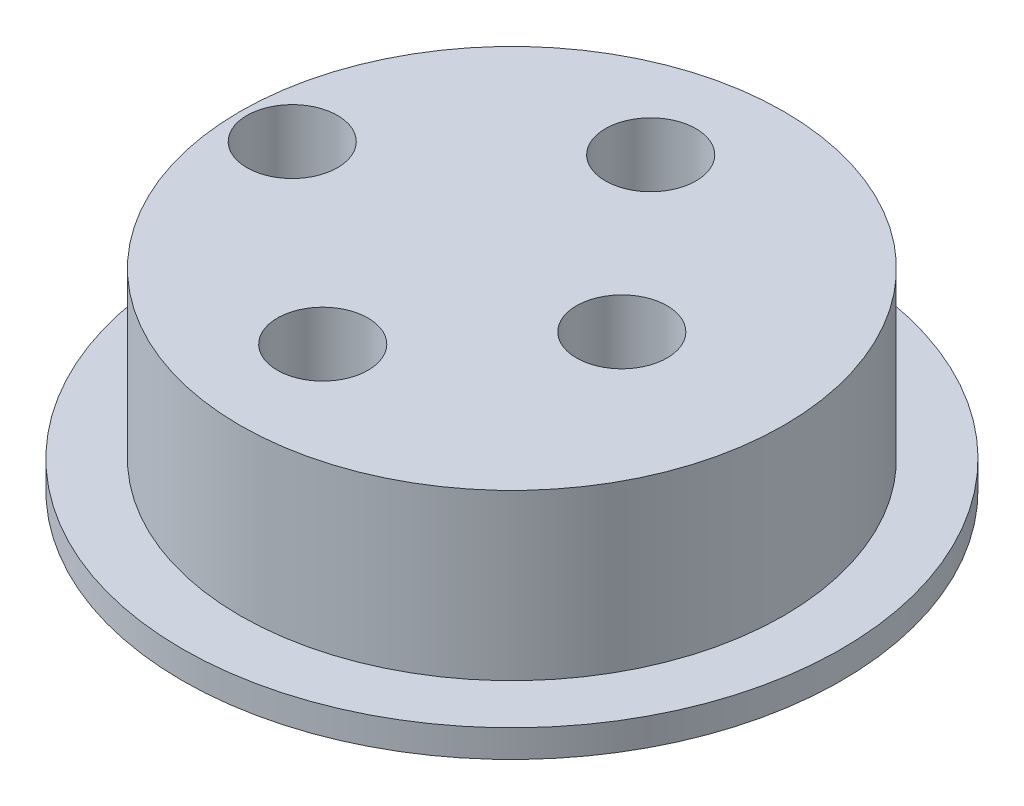
SolidWorks part; units mm, degrees
ref_plane "Front Plane" through (0, 0, 0) normal (0, 0, 1) x (1, 0, 0)
ref_plane "Top Plane" through (0, 0, 0) normal (0, 1, 0) x (1, 0, 0)
ref_plane "Right Plane" through (0, 0, 0) normal (1, 0, 0) x (0, 0, -1)
sketch "Sketch1" plane through (0, 0, 0) normal (0, 1, 0) x (1, 0, 0)
  line L0 (-2.0249, 0.1548) -> (-2.0249, 5.8286) construction
  line L1 (-2.0249, 5.8286) -> (-2.0249, -6.3704) construction
  line L2 (-2.0249, 0.1548) -> (18.99, 0.1548) construction
  line L3 (-2.0249, 0.1548) -> (-16.3494, 0.1548) construction
  line L4 (-0.0249, 0.1548) -> (-0.0249, 12.2923) construction
  line L5 (-0.0249, 12.2923) -> (-0.0249, -13.1239) construction
  line L6 (1.9751, 0.1548) -> (1.9751, 12.6475) construction
  line L7 (1.9751, 12.6475) -> (1.9751, -13.4396) construction
  line L8 (0.918, 12.2923) -> (0.918, -12.2581) construction
  circle A1 centre (1.9751, 0.1548) radius 9.9
  circle A2 centre (0.918, 6.2643) radius 1.65
  circle A4 centre (0.918, -5.6778) radius 1.65
  circle A9 centre (1.9751, 0.1548) radius 12
  circle A10 centre (-6.0249, 0.1548) radius 1.65
  circle A11 centre (5.9751, 0.1548) radius 1.65
  dimension "D4" = 19.8
  dimension "D5" = 3.3
  dimension "D7" = 3.3
  dimension "D12" = 24
  dimension "D13" = 3.3
  dimension "D14" = 3.3
  dimension "D2" = 2
  dimension "D3" = 2
  dimension "D15" = 6
  dimension "D16" = 6
extrude "Boss-Extrude1" add sketch "Sketch1" along normal blind 7 contours A1
extrude "Boss-Extrude2" add sketch "Sketch1<3>" along normal blind 1 contours A9
sketch "Sketch1<3>" plane through (0, 0, 0) normal (0, 1, 0) x (1, 0, 0) same geometry as "Sketch1"
extrude "Cut-Extrude1" cut sketch "Sketch1<4>" along normal blind 31 contours A10 | A2 | A4 | A11
sketch "Sketch1<4>" plane through (0, 0, 0) normal (0, 1, 0) x (1, 0, 0) same geometry as "Sketch1"
equation "\"R\"= 63mm"
equation "\"E\"= 2mm"
equation "\"Rr\"= 5"
equation "\"N\"= 22"
equation "\"M5\"= 5"
equation "\"SMALL_BEARING_DEPTH\"= 6MM"
